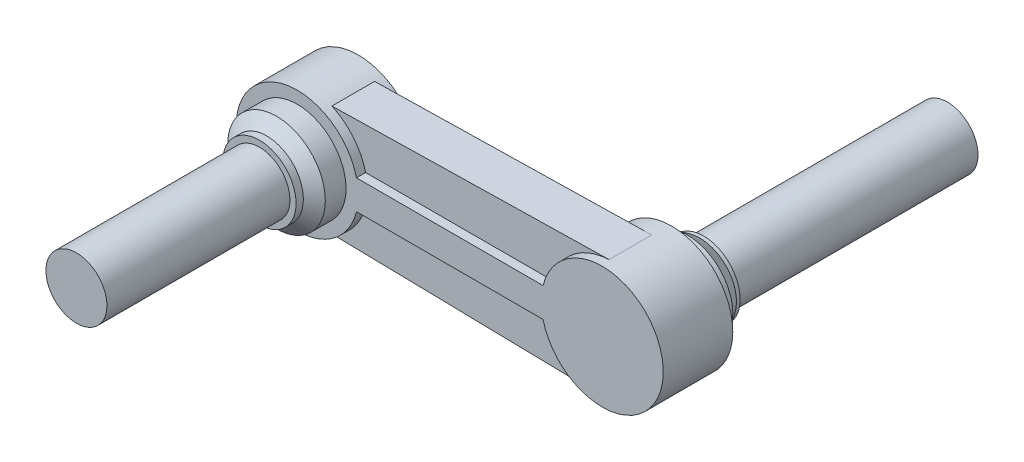
SolidWorks part; units mm, degrees
ref_plane "前视基准面" through (0, 0, 0) normal (0, 0, 1) x (1, 0, 0)
ref_plane "上视基准面" through (0, 0, 0) normal (0, 1, 0) x (1, 0, 0)
ref_plane "右视基准面" through (0, 0, 0) normal (1, 0, 0) x (0, 0, -1)
sketch "草图1" plane through (0, 0, 0) normal (0, 0, 1) x (1, 0, 0)
  circle A0 centre (0, 0) radius 25
extrude "凸台-拉伸1" add sketch "草图1" against normal blind 200
sketch "草图2" plane through (0, 0, 0) normal (0, 0, 1) x (1, 0, 0)
  circle A0 centre (0, 0) radius 30
extrude "凸台-拉伸2" add sketch "草图2" along normal blind 3
sketch "草图3" plane through (0, 0, 3) normal (0, 0, 1) x (1, 0, 0)
  circle A0 centre (0, 0) radius 37
extrude "凸台-拉伸3" add sketch "草图3" along normal blind 15
sketch "草图4" plane through (0, 0, 18) normal (0, 0, 1) x (1, 0, 0)
  circle A0 centre (0, 0) radius 50
extrude "凸台-拉伸4" add sketch "草图4" along normal blind 65
chamfer "倒角1" distance 7 distance2 10 1 edges at (37, 0, 3) first distance on face at (37, 0, 3)
chamfer "倒角2" distance 13 distance2 8 1 edges at (50, 0, 18) first distance on face at (50, 0, 18)
ref_plane "基准面1" through (0, 0, 58) normal (0, 0, 1) x (1, 0, 0)
sketch "草图5" plane through (0, 0, 58) normal (0, 0, 1) x (1, 0, 0)
  line L0 (0, 0) -> (-250, 0)
  line L1 (-250, 45) -> (-250, -45)
  line L2 (0, 50) -> (-250, 45)
  line L3 (0, -50) -> (-250, -45)
  circle A0 centre (0, 0) radius 50 construction
  circle A1 centre (0, 0) radius 50
  circle A2 centre (-250, 0) radius 45
  dimension "D1" = 45
  dimension "D2" = 45
extrude "凸台-拉伸5" add sketch "草图5" along normal mid plane 35 contours L1 A2 | L1 A2 L0 | L0 A2 L1 | A2 L0 A1 L2 | A2 L3 A1 L0 | L2 A1 L3 region at (-230.9014, -19.0986, 58) region at (-126.1174, 25.2672, 58) region at (-230.9014, 19.0986, 58) region at (-126.1174, -25.2672, 58) region at (-269.0986, 0, 58) region at (0, 0, 58)
sketch "草图6" plane through (0, 0, 58) normal (0, 0, 1) x (1, 0, 0)
  line L1 (-201.4614, -12) -> (0, -12)
  line L2 (-201.4614, 12) -> (0, 12)
  line L3 (0, 12) -> (0, -12)
  arc A0 (-201.4614, 12) -> (-201.4614, -12) centre (-250, 0) ccw
extrude "凸台-拉伸6" add sketch "草图6" along normal mid plane 50
sketch "草图7" plane through (0, 0, 83) normal (0, 0, 1) x (1, 0, 0)
  circle A0 centre (-250, 0) radius 40
extrude "凸台-拉伸7" add sketch "草图7" along normal blind 25
sketch "草图8" plane through (0, 0, 108) normal (0, 0, 1) x (1, 0, 0)
  circle A0 centre (-250, 0) radius 30
extrude "凸台-拉伸8" add sketch "草图8" along normal blind 6
chamfer "倒角3" distance 8 distance2 10 1 edges at (-210, 0, 108) first distance on face at (-210, 0, 108)
sketch "草图9" plane through (0, 0, 114) normal (0, 0, 1) x (1, 0, 0)
  circle A0 centre (-250, 0) radius 25
extrude "凸台-拉伸9" add sketch "草图9" along normal blind 150
